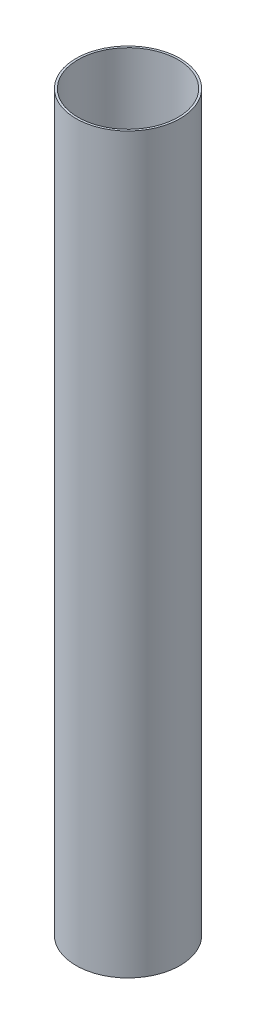
SolidWorks part; units mm, degrees
ref_plane "Front Plane" through (0, 0, 0) normal (0, 0, 1) x (1, 0, 0)
ref_plane "Top Plane" through (0, 0, 0) normal (0, 1, 0) x (1, 0, 0)
ref_plane "Right Plane" through (0, 0, 0) normal (1, 0, 0) x (0, 0, -1)
sketch "Sketch1" plane through (0, 0, 0) normal (0, 1, 0) x (1, 0, 0)
  circle A0 centre (0, 0) radius 39.7
  circle A1 centre (0, 0) radius 38.1
  dimension "D1" = 76.2
  dimension "D2" = 79.4
extrude "Boss-Extrude1" add sketch "Sketch1" along normal blind 559
